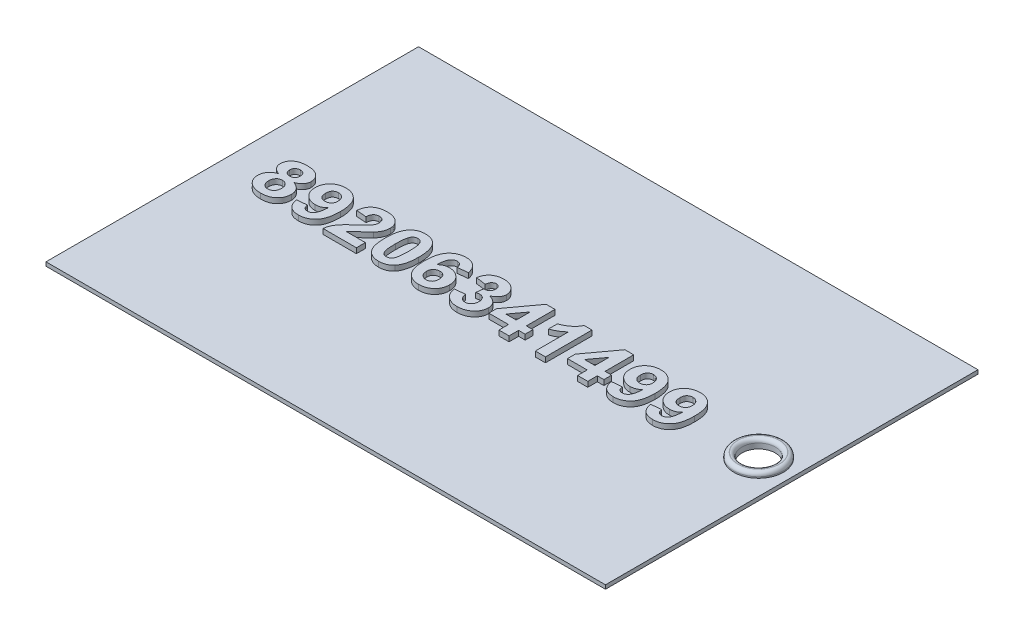
SolidWorks part; units mm, degrees
ref_plane "Спереди" through (0, 0, 0) normal (0, 0, 1) x (1, 0, 0)
ref_plane "Сверху" through (0, 0, 0) normal (0, 1, 0) x (1, 0, 0)
ref_plane "Справа" through (0, 0, 0) normal (1, 0, 0) x (0, 0, -1)
other "Configuration Table"
sketch "Эскиз1" plane through (0, 0, 0) normal (0, 1, 0) x (1, 0, 0)
  line L1 (-43.25, -28.8) -> (43.25, -28.8)
  line L2 (-43.25, -28.8) -> (-43.25, 28.8)
  line L3 (-43.25, 28.8) -> (43.25, 28.8)
  line L4 (43.25, -28.8) -> (43.25, 28.8)
  line L5 (0, 28.8) -> (0, -28.8) construction
  line L6 (-43.25, 0) -> (43.25, 0) construction
  point P0 (0, 0)
  dimension "D1" = 86.5
  dimension "D2" = 57.6
extrude "Бобышка-Вытянуть1" add sketch "Эскиз1" along normal blind 0.6
sketch "Эскиз2" plane through (0, 0.6, 0) normal (0, 1, 0) x (1, 0, 0)
  line L0 (-43.25, 0) -> (43.25, 0) construction
  line L1 (-43.25, 28.8) -> (-43.25, -28.8) construction
  line L2 (43.25, -28.8) -> (43.25, 28.8) construction
  line L3 (0, 28.8) -> (0, -28.8) construction
  line L4 (43.25, 28.8) -> (-43.25, 28.8) construction
  line L5 (-43.25, -28.8) -> (43.25, -28.8) construction
  text T0 "89206341499" font "Arial" height in points 28
extrude "Бобышка-Вытянуть2" add sketch "Эскиз2" along normal blind 0.8
sketch "Эскиз4" plane through (0, 0.6, 0) normal (0, 1, 0) x (1, 0, 0)
  line L0 (-43.25, 0) -> (43.25, 0) construction
  line L1 (-43.25, 28.8) -> (-43.25, -28.8) construction
  line L2 (43.25, -28.8) -> (43.25, 28.8) construction
  circle A0 centre (38.1303, 0) radius 3.8176
extrude "Бобышка-Вытянуть3" add sketch "Эскиз4" along normal blind 0.8
sketch "Эскиз6" plane through (0, 1.4, 0) normal (0, 1, 0) x (1, 0, 0)
  line L0 (38.1303, 3.8176) -> (38.1303, -3.8176) construction
  line L1 (34.3127, 0) -> (41.9478, 0) construction
  circle A0 centre (38.1303, 0) radius 3.8176 construction
  circle A1 centre (38.1303, 0) radius 3.8176 construction
  circle A2 centre (38.1303, 0) radius 2.579
extrude "Вырез-Вытянуть1" cut sketch "Эскиз6" against normal blind 1.8
fillet "Скругление1" radius 0.6 2 edges at (38.1303, 1.4, 3.8176) (38.1303, 1.4, 2.579)
